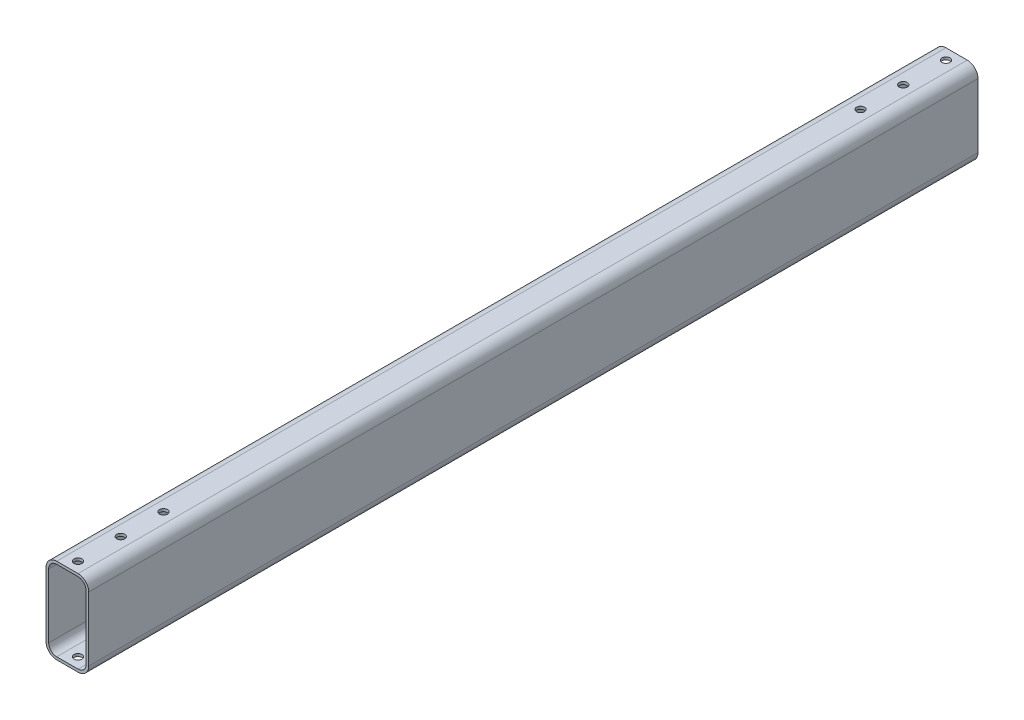
SolidWorks part; units mm, degrees
material "6061-T6 (SS)"
ref_plane "Front Plane" through (0, 0, 0) normal (0, 0, 1) x (1, 0, 0)
ref_plane "Top Plane" through (0, 0, 0) normal (0, 1, 0) x (1, 0, 0)
ref_plane "Right Plane" through (0, 0, 0) normal (1, 0, 0) x (0, 0, -1)
sketch "Sketch1" plane through (0, 0, 0) normal (0, 0, 1) x (1, 0, 0)
  line L1 (-6.35, -25.4) -> (6.35, -25.4)
  line L2 (-12.7, -19.05) -> (-12.7, 19.05)
  line L3 (-6.35, 25.4) -> (6.35, 25.4)
  line L4 (12.7, -19.05) -> (12.7, 19.05)
  line L5 (-12.7, -25.4) -> (12.7, 25.4) construction
  line L6 (-12.7, 25.4) -> (12.7, -25.4) construction
  arc A0 (-12.7, -19.05) -> (-6.35, -25.4) centre (-6.35, -19.05) ccw
  arc A1 (6.35, -25.4) -> (12.7, -19.05) centre (6.35, -19.05) ccw
  arc A2 (6.35, 25.4) -> (12.7, 19.05) centre (6.35, 19.05) cw
  arc A3 (-12.7, 19.05) -> (-6.35, 25.4) centre (-6.35, 19.05) cw
  point P0 (0, 0)
  dimension "D3" = 6.35
  dimension "D1" = 50.8
  dimension "D2" = 25.4
extrude "Extrude-Thin1" add sketch "Sketch1" along normal blind 528.701 thin thin type one direction reverse wall 1.5875
hole_wizard "3/16 (0.1875) Diameter Hole1" positions "3DSketch1" profile "Sketch3" hole size "3/16" standard "ANSI Inch" end condition through all
sketch3d "3DSketch1"
  line L1 (6.35, 25.4, 0) -> (-6.35, 25.4, 0) construction
  line L6 (0, 25.4, 528.701) -> (0, 25.4, 0) construction
  line L7 (6.35, 25.4, 528.701) -> (-6.35, 25.4, 528.701) construction
  point P57 (0, 25.4, 6.35)
  point P59 (0, 25.4, 31.75)
  point P61 (0, 25.4, 57.15)
  point P63 (0, 25.4, 496.951)
  point P65 (0, 25.4, 471.551)
  point P67 (0, 25.4, 522.351)
  dimension "D1" = 25.4
  dimension "D2" = 25.4
  dimension "D3" = 6.35
  dimension "D4" = 25.4
  dimension "D5" = 25.4
  dimension "D6" = 6.35
sketch "Sketch3" plane through (0, 25.4, 522.351) normal (1, 0, 0) x (0, 0, 1)
  line L0 (0, 0) -> (0, 50.8)
  line L1 (0, 50.8) -> (2.3812, 50.8)
  line L2 (2.3812, 50.8) -> (2.3812, 0)
  line L5 (2.3812, 0) -> (0, 0)
  line L11 (0, -6.35) -> (0, 107.95) construction
  dimension "Thru Hole Dia." = 4.7625
  dimension "Thru Hole Depth" = 50.8
hole_wizard "3/16 (0.195) Diameter Hole1" positions "Sketch4" profile "Sketch5" hole size "3/16" standard "ANSI Inch" end condition up to next
sketch "Sketch4" plane through (0, -25.4, 0) normal (0, -1, 0) x (-1, 0, 0)
  point P3 (3.175, -115.4063)
  point P6 (-3.175, -140.8063)
  point P9 (3.175, -166.2063)
  point P15 (-3.175, -394.8063)
  point P18 (3.175, -369.4063)
  point P21 (-3.175, -344.0063)
  point P29 (-3.175, -191.6063)
  point P33 (0, 0)
sketch "Sketch5" plane through (-3.175, -25.4, 115.4063) normal (1, 0, 0) x (0, 0, -1)
  line L0 (0, 0) -> (0, 1.5875)
  line L1 (0, 1.5875) -> (2.4765, 1.5875)
  line L2 (2.4765, 1.5875) -> (2.4765, 0)
  line L5 (2.4765, 0) -> (0, 0)
  line L11 (0, -6.35) -> (0, 107.95) construction
  dimension "Thru Hole Dia." = 4.953
  dimension "Thru Hole Depth" = 1.5875
